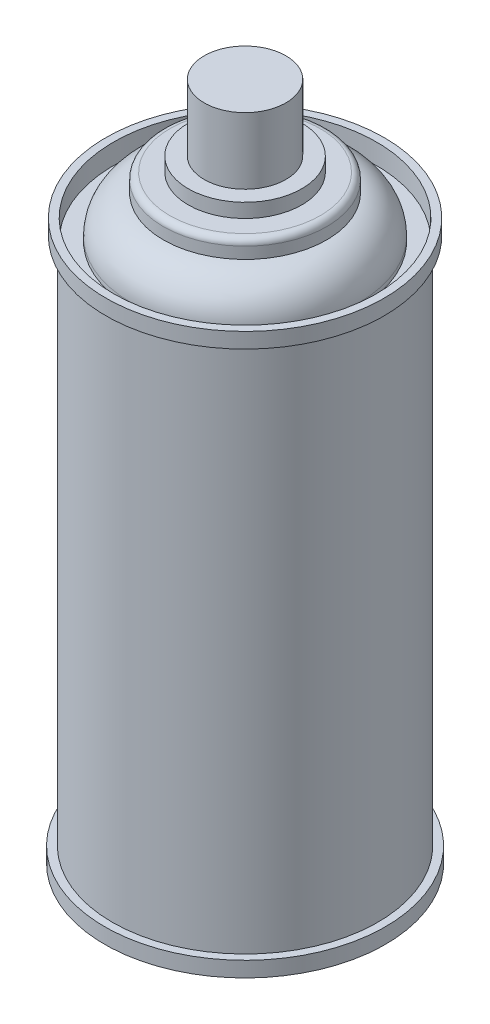
SolidWorks part; units mm, degrees
ref_plane "Front Plane" through (0, 0, 0) normal (0, 0, 1) x (1, 0, 0)
ref_plane "Top Plane" through (0, 0, 0) normal (0, 1, 0) x (1, 0, 0)
ref_plane "Right Plane" through (0, 0, 0) normal (1, 0, 0) x (0, 0, -1)
sketch "Sketch1" plane through (0, 0, 0) normal (0, 1, 0) x (1, 0, 0)
  circle A0 centre (0, 0) radius 27.94
  dimension "D1" = 55.88
extrude "Boss-Extrude1" add sketch "Sketch1" along normal blind 3.048
sketch "Sketch2" plane through (0, 3.048, 0) normal (0, 1, 0) x (1, 0, 0)
  circle A0 centre (0, 0) radius 26.416
  dimension "D1" = 52.832
extrude "Boss-Extrude2" add sketch "Sketch2" along normal blind 105.156
sketch "Sketch3" plane through (0, 108.204, 0) normal (0, 1, 0) x (1, 0, 0)
  circle A0 centre (0, 0) radius 27.686
  dimension "D1" = 55.372
extrude "Boss-Extrude3" add sketch "Sketch3" along normal blind 3.048
sketch "Sketch4" plane through (0, 111.252, 0) normal (0, 1, 0) x (1, 0, 0)
  circle A0 centre (0, 0) radius 26.162
  dimension "D1" = 52.324
extrude "Cut-Extrude1" cut sketch "Sketch4" against normal blind 4.064
sketch "Sketch5" plane through (0, 107.188, 0) normal (0, 1, 0) x (1, 0, 0)
  circle A0 centre (0, 0) radius 22.733
  dimension "D1" = 45.466
extrude "Boss-Extrude4" add sketch "Sketch5" along normal blind 8.382
sketch "Sketch6" plane through (0, 115.57, 0) normal (0, 1, 0) x (1, 0, 0)
  circle A0 centre (0, 0) radius 16.256
  dimension "D1" = 32.512
extrude "Boss-Extrude5" add sketch "Sketch6" along normal blind 3.556
sketch "Sketch7" plane through (0, 119.126, 0) normal (0, 1, 0) x (1, 0, 0)
  circle A0 centre (0, 0) radius 11.303
  dimension "D1" = 22.606
extrude "Boss-Extrude6" add sketch "Sketch7" along normal blind 2.794
sketch "Sketch8" plane through (0, 121.92, 0) normal (0, 1, 0) x (1, 0, 0)
  circle A0 centre (0, 0) radius 8.128
  dimension "D1" = 16.256
extrude "Boss-Extrude7" add sketch "Sketch8" along normal blind 13.208
fillet "Fillet1" radius 7.62 1 edges at (0, 115.57, 22.733)
fillet "Fillet2" radius 1.27 1 edges at (0, 119.126, 16.256)
